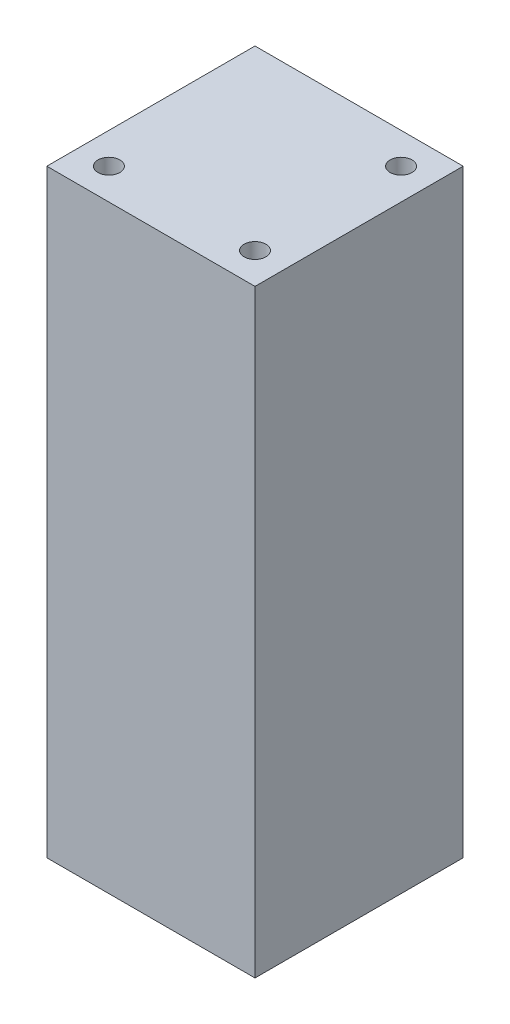
SolidWorks part; units mm, degrees
material "Oak"
ref_plane "Front Plane" through (0, 0, 0) normal (0, 0, 1) x (1, 0, 0)
ref_plane "Top Plane" through (0, 0, 0) normal (0, 1, 0) x (1, 0, 0)
ref_plane "Right Plane" through (0, 0, 0) normal (1, 0, 0) x (0, 0, -1)
sketch "Sketch1" plane through (0, 0, 0) normal (0, 1, 0) x (1, 0, 0)
  line L1 (-14.25, 14.25) -> (14.25, 14.25)
  line L2 (-14.25, 14.25) -> (-14.25, -14.25)
  line L3 (-14.25, -14.25) -> (14.25, -14.25)
  line L4 (14.25, 14.25) -> (14.25, -14.25)
  line L5 (-14.25, 14.25) -> (14.25, -14.25) construction
  line L6 (-14.25, -14.25) -> (14.25, 14.25) construction
  point P0 (0, 0)
  dimension "D1" = 28.5
extrude "Boss-Extrude1" add sketch "Sketch1" along normal blind 82
sketch "Sketch2" plane through (0, 82, 0) normal (0, 1, 0) x (1, 0, 0)
  circle A0 centre (10, 10) radius 1.5
  circle A1 centre (10, -10) radius 1.5
  circle A2 centre (-10, -10) radius 1.5
  dimension "D1" = 3
  dimension "D2" = 3
  dimension "D3" = 3
  dimension "D4" = 20
  dimension "D5" = 20
extrude "Cut-Extrude1" cut sketch "Sketch2" against normal blind 12
